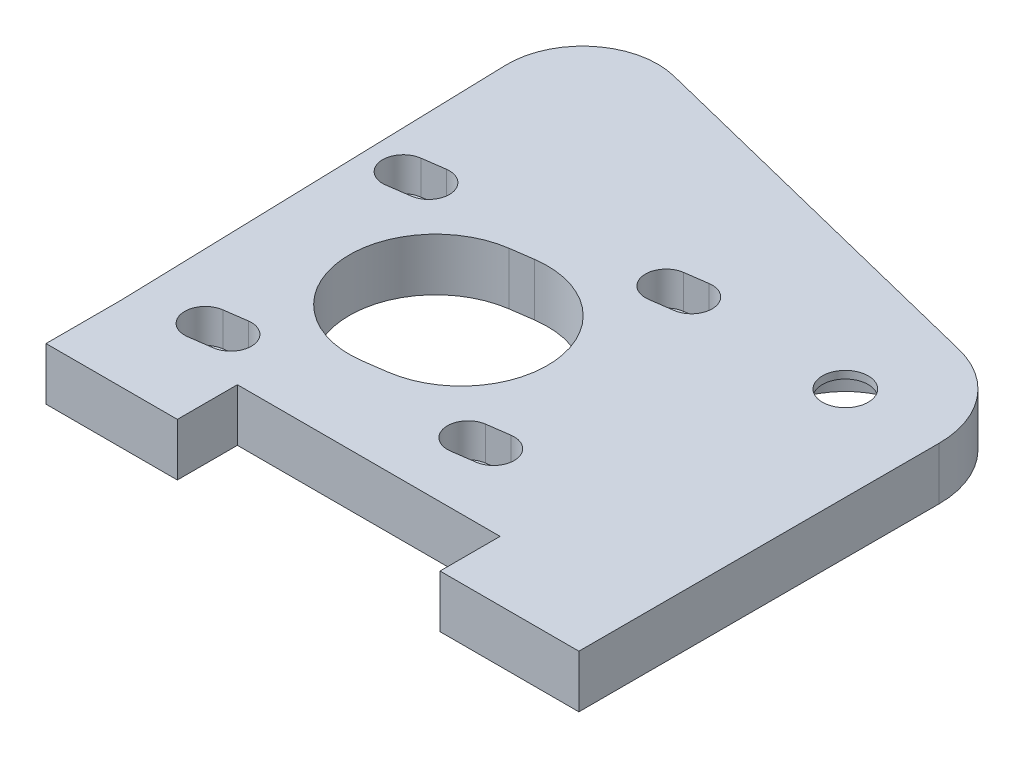
SolidWorks part; units mm, degrees
note: The reader was unsure of these and kept them because the rebuilt part matched: shared geometry of "Sketch2<7>", "Sketch2<8>".
ref_plane "Front" through (0, 0, 0) normal (0, 0, 1) x (1, 0, 0)
ref_plane "Top" through (0, 0, 0) normal (0, 1, 0) x (1, 0, 0)
ref_plane "Right" through (0, 0, 0) normal (1, 0, 0) x (0, 0, -1)
sketch "Sketch2" plane through (0, 0, 0) normal (0, 1, 0) x (1, 0, 0)
  line L0 (-101.1698, 0) -> (151.9116, 0) construction
  line L1 (0, 0) -> (133.1277, 18.7099) construction
  line L2 (52.9793, 7.4458) -> (55.9501, 7.8633) construction
  line L3 (51.3789, 18.8338) -> (54.3497, 19.2514)
  line L4 (54.5798, -3.9423) -> (57.5506, -3.5248)
  line L5 (50.7009, 34.4356) -> (58.2286, -19.1265) construction
  line L6 (22.0885, -12.548) -> (91.1553, -2.8413) construction
  line L11 (17.7742, 18.1503) -> (86.8409, 27.857) construction
  line L12 (66.1713, 24.9521) -> (69.1421, 25.3696) construction
  line L13 (65.7886, 27.6753) -> (68.7594, 28.0929)
  line L14 (65.9626, 26.4375) -> (68.9334, 26.855)
  line L15 (66.3801, 23.4667) -> (69.3509, 23.8842)
  line L16 (66.554, 22.2289) -> (69.5248, 22.6464)
  line L17 (70.4857, -5.7462) -> (73.4565, -5.3287) construction
  line L18 (70.6944, -7.2316) -> (73.6652, -6.8141)
  line L19 (70.2769, -4.2608) -> (73.2477, -3.8433)
  line L20 (70.8684, -8.4694) -> (73.8392, -8.0519)
  line L21 (70.103, -3.023) -> (73.0738, -2.6055)
  line L22 (42.7582, -9.6431) -> (39.7874, -10.0606) construction
  line L23 (42.9669, -11.1285) -> (39.9961, -11.546)
  line L24 (42.5494, -8.1577) -> (39.5786, -8.5752)
  line L25 (38.4438, 21.0553) -> (35.473, 20.6377) construction
  line L26 (38.235, 22.5407) -> (35.2642, 22.1231)
  line L27 (38.6526, 19.5699) -> (35.6818, 19.1523)
  line L28 (38.0611, 23.7785) -> (35.0903, 23.361)
  line L29 (38.8265, 18.332) -> (35.8557, 17.9145)
  line L30 (42.3754, -6.9198) -> (39.4046, -7.3373)
  line L31 (43.1409, -12.3663) -> (40.1701, -12.7838)
  line L34 (90.012, 24.9921) -> (40.012, 24.9921) construction
  line L35 (40.012, 24.9921) -> (40.012, 39.9921) construction
  line L36 (54.4647, 7.6545) -> (99.593, 29.6651) construction
  line L39 (102.512, 24.9921) -> (102.512, -23.0079)
  line L40 (102.512, -23.0079) -> (84.012, -23.0079)
  line L41 (42.4235, 49.697) -> (93.0264, 37.1232)
  line L42 (31.512, -23.0079) -> (31.512, -13.0079)
  line L43 (31.512, -13.0079) -> (30.0161, 39.7084)
  line L44 (49.012, -23.0079) -> (49.012, -15.0079)
  line L45 (49.012, -15.0079) -> (84.012, -15.0079)
  line L46 (84.012, -15.0079) -> (84.012, -23.0079)
  line L47 (49.012, -23.0079) -> (31.512, -23.0079)
  arc A1 (51.3789, 18.8338) -> (54.5798, -3.9423) centre (52.9793, 7.4458) ccw
  arc A2 (57.5506, -3.5248) -> (54.3497, 19.2514) centre (55.9501, 7.8633) ccw
  arc A3 (65.9626, 26.4375) -> (66.3801, 23.4667) centre (66.1713, 24.9521) ccw
  arc A4 (69.3509, 23.8842) -> (68.9334, 26.855) centre (69.1421, 25.3696) ccw
  arc A5 (69.5248, 22.6464) -> (68.7594, 28.0929) centre (69.1421, 25.3696) ccw
  arc A6 (65.7886, 27.6753) -> (66.554, 22.2289) centre (66.1713, 24.9521) ccw
  arc A7 (70.6944, -7.2316) -> (70.2769, -4.2608) centre (70.4857, -5.7462) cw
  arc A8 (73.2477, -3.8433) -> (73.6652, -6.8141) centre (73.4565, -5.3287) cw
  arc A9 (73.0738, -2.6055) -> (73.8392, -8.0519) centre (73.4565, -5.3287) cw
  arc A10 (70.8684, -8.4694) -> (70.103, -3.023) centre (70.4857, -5.7462) cw
  arc A11 (42.9669, -11.1285) -> (42.5494, -8.1577) centre (42.7582, -9.6431) ccw
  arc A12 (39.5786, -8.5752) -> (39.9961, -11.546) centre (39.7874, -10.0606) ccw
  arc A13 (38.235, 22.5407) -> (38.6526, 19.5699) centre (38.4438, 21.0553) cw
  arc A14 (35.6818, 19.1523) -> (35.2642, 22.1231) centre (35.473, 20.6377) cw
  arc A15 (35.8557, 17.9145) -> (35.0903, 23.361) centre (35.473, 20.6377) cw
  arc A16 (38.0611, 23.7785) -> (38.8265, 18.332) centre (38.4438, 21.0553) cw
  arc A17 (39.4046, -7.3373) -> (40.1701, -12.7838) centre (39.7874, -10.0606) ccw
  arc A18 (43.1409, -12.3663) -> (42.3754, -6.9198) centre (42.7582, -9.6431) ccw
  circle A20 centre (90.012, 24.9921) radius 9.5
  arc A21 (102.512, 24.9921) -> (93.0264, 37.1232) centre (90.012, 24.9921) ccw
  circle A22 centre (40.012, 39.9921) radius 6.5
  arc A25 (42.4235, 49.697) -> (30.0161, 39.7084) centre (40.012, 39.9921) ccw
  circle A26 centre (90.012, 24.9921) radius 3.05
  circle A27 centre (40.012, 39.9921) radius 2
  point P7 (52.9793, 7.4458)
  point P8 (55.9501, 7.8633)
  point P11 (54.4647, 7.6545)
  point P16 (41.2728, -9.8518)
  point P19 (54.4647, 7.6545)
  point P21 (71.9711, -5.5375)
  point P23 (56.6219, -7.6946)
  point P25 (36.9584, 20.8465)
  point P28 (67.6567, 25.1609)
  point P32 (67.6567, 25.1609)
  point P43 (71.9711, -5.5375)
  point P56 (41.2728, -9.8518)
  point P63 (36.9584, 20.8465)
  point P88 (90.012, 24.9921)
  dimension "D2" = 3
  dimension "D9" = 18
  dimension "D10" = 39.55
  dimension "D13" = 13
  dimension "D14" = 11.5
  dimension "D15" = 2.75
  dimension "D16" = 20
  dimension "D17" = 48
  dimension "D3" = 19
  dimension "D4" = 25
  dimension "D18" = 10
  dimension "D23" = 6.1
  dimension "D24" = 4
  dimension "D1" = 8
  dimension "D5" = 15.5
  dimension "D6" = 15.5
  dimension "D7" = 1.25
  dimension "D8" = 55
  dimension "D11" = 50
  dimension "D12" = 15
  dimension "D19" = 8
  dimension "D20" = 35
  dimension "D21" = 71
  dimension "D22" = 17.5
extrude "Boss-Extrude1" add sketch "Sketch2" along normal blind 7 contours L41 A25 L43 L42 L47 L44 L45 L46 L40 L39 A21 L28 A16 L29 A15 A2 L4 A1 L3 A6 L13 A5 L16 L20 A10 L21 A9 A18 L31 A17 L30 A20 A22 | L13 A6 L16 A5 A4 L15 A3 L14 | L15 A4 L14 A3 | A14 L27 A13 L26 | A16 L28 A15 L29 L27 A14 L26 A13 | L31 A18 L30 A17 A12 L24 A11 L23 | L24 A12 L23 A11 | A8 L19 A7 L18 | A10 L20 A9 L21 L19 A8 L18 A7 | A20 A26 | A22 A27
extrude "Cut-Extrude1" cut sketch "Sketch2<7>" along normal blind 6 contours A20 A26
sketch "Sketch2<7>" plane through (0, 0, 0) normal (0, 1, 0) x (1, 0, 0) same geometry as "Sketch2"
extrude "Cut-Extrude2" cut sketch "Sketch2<8>" against normal blind 4.5 from surface at 7 contours L13 A5 L16 A6 | L28 A15 L29 A16 | L30 A17 L31 A18 | L21 A9 L20 A10 starting at face at (71.9711, 7, 5.5375)
sketch "Sketch2<8>" plane through (0, 0, 0) normal (0, 1, 0) x (1, 0, 0) same geometry as "Sketch2"
